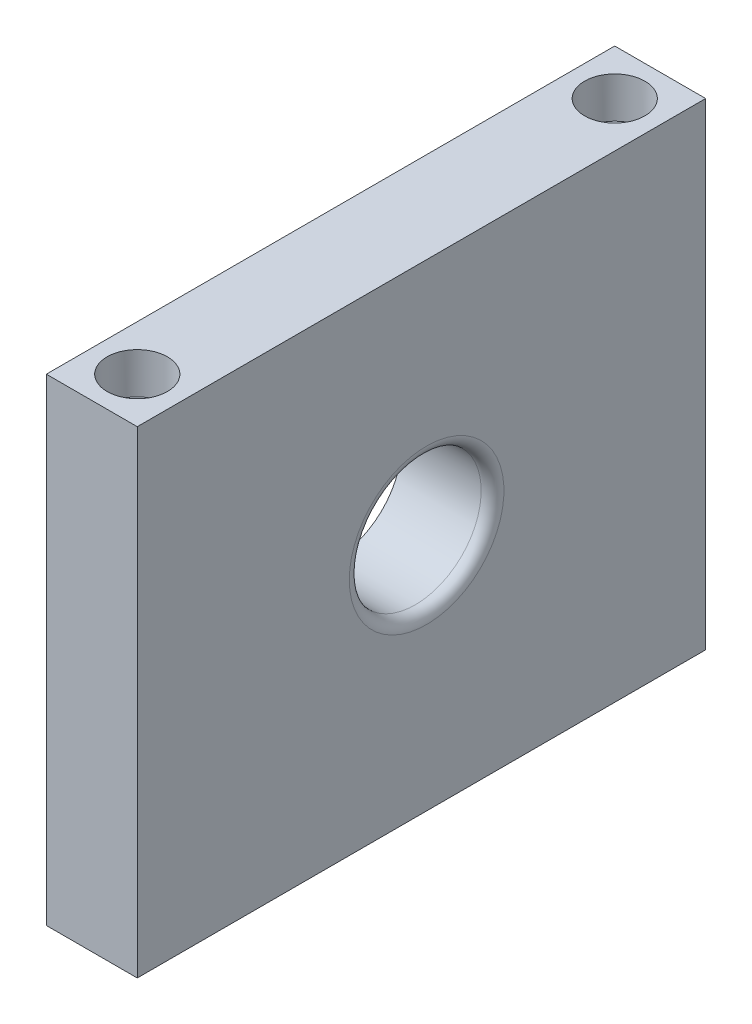
SolidWorks part; units mm, degrees
ref_plane "Front Plane" through (0, 0, 0) normal (0, 0, 1) x (1, 0, 0)
ref_plane "Top Plane" through (0, 0, 0) normal (0, 1, 0) x (1, 0, 0)
ref_plane "Right Plane" through (0, 0, 0) normal (1, 0, 0) x (0, 0, -1)
sketch "Sketch1" plane through (0, 0, 0) normal (0, 1, 0) x (1, 0, 0)
  line L1 (-10.223, 36.3848) -> (14.777, 36.3848)
  line L2 (-10.223, 36.3848) -> (-10.223, -13.6152)
  line L3 (-10.223, -13.6152) -> (14.777, -13.6152)
  line L4 (14.777, 36.3848) -> (14.777, -13.6152)
  circle A0 centre (1.277, 11.3848) radius 3.4
  dimension "D3" = 6.8
  dimension "D1" = 50
  dimension "D2" = 25
  dimension "D4" = 13.5
  dimension "D5" = 25
extrude "Boss-Extrude1" add sketch "Sketch1" along normal blind 3
sketch "Sketch2" plane through (-10.223, 0, 0) normal (-1, 0, 0) x (0, 0, 1)
  line L0 (18.15, 0) -> (-18.15, 0) construction
  line L1 (-36.3848, 3) -> (13.6152, 3)
  line L2 (-36.3848, 3) -> (-36.3848, 0)
  line L3 (-36.3848, 0) -> (13.6152, 0)
  line L4 (13.6152, 3) -> (13.6152, 0)
  line L5 (13.6152, 3) -> (13.6152, 0) construction
extrude "Boss-Extrude2" add sketch "Sketch2" along normal blind 8
sketch "Sketch3" plane through (0, 0, 0) normal (0, -1, 0) x (1, 0, 0)
  line L0 (-18.223, 13.6152) -> (14.777, 13.6152) construction
  line L1 (-18.223, -36.3848) -> (-10.223, -36.3848)
  line L2 (-18.223, -36.3848) -> (-18.223, 13.6152)
  line L3 (-18.223, 13.6152) -> (-10.223, 13.6152)
  line L4 (-10.223, -36.3848) -> (-10.223, 13.6152)
  dimension "D1" = 8
extrude "Boss-Extrude3" add sketch "Sketch3" along normal blind 42
sketch "Sketch4" plane through (0, 3, 0) normal (0, 1, 0) x (1, 0, 0)
  line L0 (-18.223, -13.6152) -> (-18.223, 36.3848) construction
  line L1 (14.777, 36.3848) -> (-18.223, 36.3848) construction
  line L2 (-18.223, -13.6152) -> (14.777, -13.6152) construction
  circle A0 centre (-14.223, 32.3848) radius 2.65
  circle A1 centre (-14.223, -9.6152) radius 2.65
  dimension "D2" = 5.3
  dimension "D4" = 5.3
  dimension "D5" = 4
  dimension "D6" = 4
  dimension "D1" = 4
  dimension "D3" = 4
extrude "Cut-Extrude1" cut sketch "Sketch4" against normal blind 6.6
ref_plane "Plane1" through (0, -19.5, 0) normal (0, 1, 0) x (1, 0, 0)
mirror "Mirror1" about plane through (0, -19.5, 0) normal (0, 1, 0) of "Cut-Extrude1"
sketch "Sketch5" plane through (-18.223, 0, 0) normal (-1, 0, 0) x (0, 0, 1)
  line L0 (18.15, 0) -> (-18.15, 0) construction
  line L1 (-6.9841, -24.1818) -> (-6.6547, -18.3888) construction
  line L2 (-6.6547, -18.3888) -> (-11.5069, -15.207) construction
  line L3 (-11.5069, -15.207) -> (-16.6885, -17.8182) construction
  line L4 (-16.6885, -17.8182) -> (-17.0179, -23.6112) construction
  line L5 (-17.0179, -23.6112) -> (-12.1657, -26.793) construction
  line L6 (-12.1657, -26.793) -> (-6.9841, -24.1818) construction
  circle A0 centre (-11.8363, -21) radius 5.025 construction
  circle A1 centre (-11.8363, -21) radius 5.8024
  dimension "D1" = 21
  dimension "D2" = 10.05
extrude "Cut-Extrude2" cut sketch "Sketch5" against normal blind 9
fillet "Fillet2" radius 1 1 edges at (-10.223, -21, -6.0339)
ref_plane "Plane2" through (-1.723, 0, 0) normal (-1, 0, 0) x (0, 0, 1)
mirror "Mirror2" about plane through (-1.723, 0, 0) normal (-1, 0, 0) of "Cut-Extrude1"
sketch "Sketch6" plane through (0, 3, 0) normal (0, 1, 0) x (1, 0, 0)
  line L0 (1.277, 14.7848) -> (1.277, 7.9848) construction
  line L1 (14.777, -13.6152) -> (14.777, 36.3848) construction
  line L2 (14.777, 16.9444) -> (14.777, 5.8251)
  circle A0 centre (1.277, 11.3848) radius 3.4 construction
  circle A1 centre (1.277, 11.3848) radius 3.1
  circle A2 centre (1.277, 11.3848) radius 12.6
  arc A3 (14.777, 16.9444) -> (14.777, 5.8251) centre (1.277, 11.3848) ccw
  line M9 (14.777, -13.6152) -> (14.777, 36.3848)
  dimension "D1" = 25.2
  dimension "D2" = 2
extrude "Boss-Extrude4" add sketch "Sketch6" along normal blind 2 contours A3 A2 M9
fillet "Fillet4" radius 1 1 edges at (14.777, 5, -11.3848)
sketch "Sketch8" plane through (0, 3, 0) normal (0, 1, 0) x (1, 0, 0)
  line L0 (4.677, 11.3848) -> (-2.123, 11.3848) construction
  circle A0 centre (1.277, 11.3848) radius 3.4 construction
  circle A1 centre (1.277, 19.8848) radius 1.5898
  circle A2 centre (1.277, 2.8848) radius 1.7774
  point P9 (1.277, 11.3848)
  dimension "D1" = 8.5
  dimension "D2" = 8.5
extrude "Cut-Extrude3" cut sketch "Sketch8" against normal blind 10
sketch "Sketch9" plane through (0, 0, 13.6152) normal (0, 0, 1) x (1, 0, 0)
  line L1 (14.777, 0) -> (-34.2447, 0)
  line L2 (14.777, 0) -> (14.777, 20.9769)
  line L3 (14.777, 20.9769) -> (-34.2447, 20.9769)
  line L4 (-34.2447, 0) -> (-34.2447, 20.9769)
extrude "Cut-Extrude4" cut sketch "Sketch9" against normal through all
sketch "Sketch10" plane through (0, -3.6, 0) normal (0, 1, 0) x (1, 0, 0)
  line L0 (-14.223, 35.0348) -> (-14.223, 29.7348) construction
  circle A0 centre (-14.223, 32.3848) radius 2.65 construction
  circle A1 centre (-14.223, 32.3848) radius 2.65 construction
  circle A2 centre (-14.223, 32.3848) radius 1.4
  dimension "D1" = 2.8
extrude "Cut-Extrude5" cut sketch "Sketch10" against normal through all
ref_plane "Plane3" through (0, 0, -11.3848) normal (0, 0, 1) x (1, 0, 0)
mirror "Mirror3" about plane through (0, 0, -11.3848) normal (0, 0, 1) of "Cut-Extrude5"
